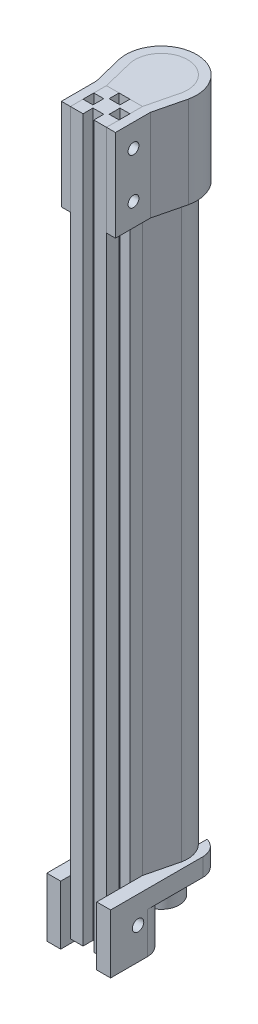
SolidWorks part; units mm, degrees
material "A286 Iron Base Superalloy"
ref_plane "Front Plane" through (0, 0, 0) normal (0, 0, 1) x (1, 0, 0)
ref_plane "Top Plane" through (0, 0, 0) normal (0, 1, 0) x (1, 0, 0)
ref_plane "Right Plane" through (0, 0, 0) normal (1, 0, 0) x (0, 0, -1)
sketch "Sketch1" plane through (0, 0, 0) normal (0, 1, 0) x (1, 0, 0)
  line L0 (14.2987, -2.9258) -> (10, -20.405)
  line L1 (10, -20.405) -> (-10, -20.405)
  line L2 (-10, -20.405) -> (-14.2987, -2.9258)
  line L3 (0, 14.595) -> (-46.807, 14.595) construction
  arc A0 (14.2987, -2.9258) -> (-14.2987, -2.9258) centre (0, 0) ccw
  point P1 (14.4842, 1.795)
  point P9 (-14.4842, 1.795)
  point P10 (0, -20.405)
  point P11 (-9.9858, -16.205)
  point P12 (14.4842, 1.795)
  point P13 (0, 0)
  point P14 (14.4842, 1.795)
  point P15 (14.4842, 1.795)
  point P16 (14.2786, -3.0226)
  point P17 (14.0888, -3.8105)
  point P18 (0, 0)
  point P19 (14.2691, -3.0673)
  point P20 (8.7812, -20.405)
  dimension "D1" = 29.19
  dimension "D2" = 18
  dimension "D3" = 35
  dimension "D4" = 20
extrude "Boss-Extrude1" add sketch "Sketch1" along normal blind 369.57
sketch "Sketch2" plane through (0, 369.57, 0) normal (0, 1, 0) x (1, 0, 0)
  line L0 (-10, -20.405) -> (10, -20.405) construction
  line L1 (-10, -20.405) -> (10, -20.405)
  line L2 (-10, -20.405) -> (-10, -40.405)
  line L3 (-10, -40.405) -> (10, -40.405)
  line L4 (10, -20.405) -> (10, -40.405)
  point P8 (0, -20.405)
  point P9 (0, -20.405)
  dimension "D1" = 20
extrude "Boss-Extrude2" add sketch "Sketch2" against normal blind 400 separate body
sketch "Sketch7" plane through (0, 369.57, 0) normal (0, 1, 0) x (1, 0, 0)
  line L0 (10, -40.405) -> (10, -20.405) construction
  line L1 (10, -27.405) -> (4.5, -27.405)
  line L2 (10, -27.405) -> (10, -33.405)
  line L3 (10, -33.405) -> (4.5, -33.405)
  line L4 (4.5, -27.405) -> (4.5, -33.405)
  line L5 (0, -40.405) -> (0, 0) construction
  line L6 (-10, -40.405) -> (10, -40.405) construction
  line L7 (-10, -27.405) -> (-10, -33.405)
  line L8 (-10, -33.405) -> (-4.5, -33.405)
  line L9 (-4.5, -27.405) -> (-4.5, -33.405)
  line L10 (-10, -27.405) -> (-4.5, -27.405)
  line L11 (-10, -20.405) -> (10, -20.405) construction
  line L12 (-3, -20.405) -> (3, -20.405)
  line L13 (-3, -20.405) -> (-3, -25.905)
  line L14 (-3, -25.905) -> (3, -25.905)
  line L15 (3, -20.405) -> (3, -25.905)
  line L16 (-10, -30.405) -> (10, -30.405) construction
  line L17 (-3, -34.905) -> (3, -34.905)
  line L18 (3, -40.405) -> (3, -34.905)
  line L19 (-3, -40.405) -> (3, -40.405)
  line L20 (-3, -40.405) -> (-3, -34.905)
  point P12 (10, -30.405)
  point P13 (10, -30.405)
  point P25 (0, -20.405)
  dimension "D1" = 6
  dimension "D2" = 5.5
  dimension "D3" = 5.5
  dimension "D4" = 6
extrude "Cut-Extrude3" cut sketch "Sketch7" against normal through all
sketch "Sketch8" plane through (0, 369.57, 0) normal (0, 1, 0) x (1, 0, 0)
  line L0 (-10, -40.405) -> (-10, -20.405)
  line L1 (-10, -33.405) -> (-10, -40.405) construction
  line L2 (-14.2987, -2.9258) -> (-10, -20.405) construction
  line L3 (-10, -20.405) -> (-14.2987, -2.9258)
  line L4 (14.2987, -2.9258) -> (10, -20.405)
  line L5 (10, -20.405) -> (14.2987, -2.9258) construction
  line L6 (10, -20.405) -> (10, -40.405)
  line L7 (10, -40.405) -> (10, -33.405) construction
  line L8 (-15, -40.405) -> (-15, -21.0108)
  line L9 (-15, -21.0108) -> (-19.1758, -4.0315)
  line L10 (19.1758, -4.0315) -> (15, -21.0108)
  line L11 (15, -21.0108) -> (15, -40.405)
  line L12 (-15, -40.405) -> (-10, -40.405)
  line L13 (10, -40.405) -> (15, -40.405)
  line L14 (-10, -33.405) -> (-4.5, -33.405) construction
  arc A0 (-14.2987, -2.9258) -> (14.2987, -2.9258) centre (0, 0) cw
  arc A1 (14.2987, -2.9258) -> (-14.2987, -2.9258) centre (0, 0) ccw construction
  arc A2 (-19.1758, -4.0315) -> (19.1758, -4.0315) centre (0, 0) cw
  dimension "D1" = 5
  dimension "D2" = 7
extrude "Boss-Extrude3" add sketch "Sketch8" against normal blind 50.8 separate body
sketch "Sketch9" plane through (-15, 0, 0) normal (-1, 0, 0) x (0, 0, 1)
  line L0 (40.405, 344.17) -> (-19.595, 344.17) construction
  line L1 (40.405, 318.77) -> (40.405, 369.57) construction
  line L2 (-19.595, 369.57) -> (-19.595, 318.77) construction
  line L3 (33.405, -30.43) -> (33.405, 369.57) construction
  line L5 (21.0108, 369.57) -> (40.405, 369.57) construction
  circle A0 centre (30.405, 356.87) radius 3
  circle A1 centre (30.405, 331.47) radius 3
  dimension "D1" = 6
  dimension "D2" = 12.7
extrude "Cut-Extrude4" cut sketch "Sketch9" against normal through all
sketch "Sketch10" plane through (0, 0, 0) normal (0, -1, 0) x (1, 0, 0)
  circle A0 centre (0, 0) radius 9.975
  dimension "D1" = 19.95
extrude "Boss-Extrude4" add sketch "Sketch10" along normal blind 24.4221
sketch "Sketch11" plane through (0, 0, 0) normal (0, -1, 0) x (1, 0, 0)
  line L0 (-10, 20.405) -> (10, 20.405) construction
  line L1 (-17.7, 10.405) -> (17.7, 10.405)
  line L2 (-17.7, 10.405) -> (-17.7, 20.405)
  line L3 (-17.7, 20.405) -> (17.7, 20.405)
  line L4 (17.7, 10.405) -> (17.7, 20.405)
  point P6 (0, 20.405)
  dimension "D1" = 10
  dimension "D2" = 35.4
extrude "Boss-Extrude5" add sketch "Sketch11" along normal blind 10 separate body
sketch "Sketch12" plane through (0, -10, 0) normal (0, -1, 0) x (1, 0, 0)
  line L1 (-17.7, 20.405) -> (17.7, 20.405)
  line L2 (-17.7, 20.405) -> (-17.7, 15.405)
  line L3 (-17.7, 15.405) -> (17.7, 15.405)
  line L4 (17.7, 20.405) -> (17.7, 15.405)
  line L5 (17.7, 10.405) -> (17.7, 20.405) construction
  dimension "D1" = 5
  dimension "D2" = 35.4
extrude "Boss-Extrude6" add sketch "Sketch12" along normal blind 22.7
sketch "Sketch14" plane through (0, 0, 15.405) normal (0, 0, -1) x (-1, 0, 0)
  line L0 (17.7, -10) -> (-17.7, -10) construction
  circle A0 centre (0, -15) radius 3.175
  dimension "D1" = 6.35
  dimension "D2" = 5
extrude "Cut-Extrude5" cut sketch "Sketch14" against normal through all
sketch "Sketch15" plane through (0, 0, 20.405) normal (0, 0, 1) x (1, 0, 0)
  line L0 (-10, -30.43) -> (-10, 369.57) construction
  line L1 (-17.7, 0) -> (-10, 0)
  line L2 (-17.7, 0) -> (-17.7, -32.7)
  line L3 (-17.7, -32.7) -> (-10, -32.7)
  line L4 (-10, 0) -> (-10, -32.7)
  line L5 (17.7, -32.7) -> (-17.7, -32.7) construction
  line L6 (10, -30.43) -> (10, 369.57) construction
  line L7 (10, 0) -> (17.7, 0)
  line L8 (10, 0) -> (10, -32.7)
  line L9 (10, -32.7) -> (17.7, -32.7)
  line L10 (17.7, 0) -> (17.7, -32.7)
  line L11 (17.7, 0) -> (-17.7, 0) construction
extrude "Boss-Extrude7" add sketch "Sketch15" along normal blind 25.4
sketch "Sketch16" plane through (17.7, 0, 0) normal (1, 0, 0) x (0, 0, -1)
  line L2 (-10.405, -10) -> (-15.405, -10) construction
  line L3 (-27.405, -30.43) -> (-27.405, 331.47) construction
  circle A0 centre (-30.58, -15) radius 3.175
  dimension "D1" = 6.35
  dimension "D2" = 5
extrude "Cut-Extrude6" cut sketch "Sketch16" against normal through all
sketch "Sketch17" plane through (0, 0, 10.405) normal (0, 0, -1) x (-1, 0, 0)
  line L1 (17.7, -10) -> (10.475, -10)
  line L2 (17.7, -10) -> (17.7, 0)
  line L3 (17.7, 0) -> (10.475, 0)
  line L4 (10.475, -10) -> (10.475, 0)
  line L5 (9.975, -24.4221) -> (9.975, 0) construction
  line L6 (0, -32.7) -> (0, 0) construction
  line L7 (17.7, -32.7) -> (-17.7, -32.7) construction
  line L8 (-17.7, 0) -> (-10.475, 0)
  line L9 (-10.475, -10) -> (-10.475, 0)
  line L10 (-17.7, -10) -> (-10.475, -10)
  line L11 (-17.7, -10) -> (-17.7, 0)
  line L12 (17.7, 0) -> (-17.7, 0) construction
  dimension "D1" = 0.5
extrude "Boss-Extrude8" add sketch "Sketch17" along normal blind 25.4
fillet "Fillet1" radius 10 4 edges at (17.7, -21.35, 15.405) (-17.7, -21.35, 15.405) (17.7, -5, -14.995) (-17.7, -5, -14.995)
